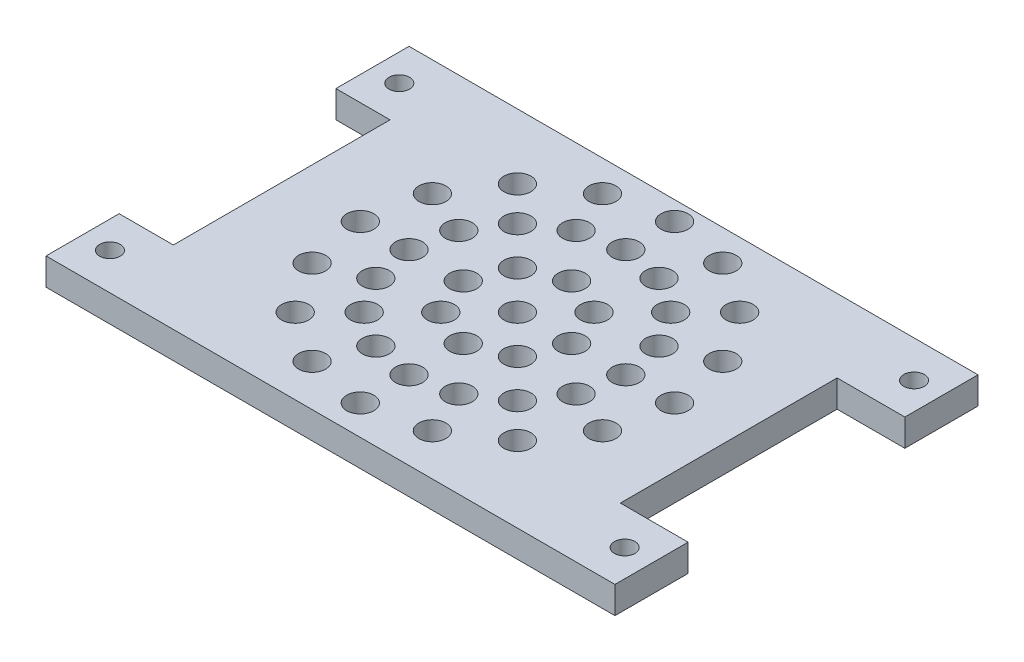
SolidWorks part; units mm, degrees
material "1060 Alloy"
ref_plane "Front Plane" through (0, 0, 0) normal (0, 0, 1) x (1, 0, 0)
ref_plane "Top Plane" through (0, 0, 0) normal (0, 1, 0) x (1, 0, 0)
ref_plane "Right Plane" through (0, 0, 0) normal (1, 0, 0) x (0, 0, -1)
sketch "Sketch1" plane through (0, 0, 0) normal (0, 1, 0) x (1, 0, 0)
  line L1 (-45.1884, 47.6545) -> (88.1616, 47.6545)
  line L2 (-45.1884, 47.6545) -> (-45.1884, -37.4355)
  line L3 (-45.1884, -37.4355) -> (88.1616, -37.4355)
  line L4 (88.1616, 47.6545) -> (88.1616, -37.4355)
  dimension "D1" = 133.35
  dimension "D2" = 85.09
extrude "Boss-Extrude1" add sketch "Sketch1" along normal blind 6.35
sketch "Sketch4" plane through (0, 6.35, 0) normal (0, 1, 0) x (1, 0, 0)
  line L0 (88.1616, -37.4355) -> (88.1616, 47.6545) construction
  line L1 (88.1616, 30.5095) -> (72.2866, 30.5095)
  line L2 (88.1616, 30.5095) -> (88.1616, -20.2905)
  line L3 (88.1616, -20.2905) -> (72.2866, -20.2905)
  line L4 (72.2866, 30.5095) -> (72.2866, -20.2905)
  line L5 (21.4866, 47.6545) -> (21.4866, -37.4355) construction
  line L6 (88.1616, 47.6545) -> (-45.1884, 47.6545) construction
  line L7 (-45.1884, -37.4355) -> (88.1616, -37.4355) construction
  line L12 (-45.1884, 5.1095) -> (88.1616, 5.1095) construction
  line L13 (-45.1884, 30.5095) -> (-45.1884, -20.2905)
  line L14 (-45.1884, 30.5095) -> (-32.4884, 30.5095)
  line L15 (-45.1884, -20.2905) -> (-32.4884, -20.2905)
  line L16 (-32.4884, 30.5095) -> (-32.4884, -20.2905)
  line L17 (-45.1884, 47.6545) -> (-45.1884, -37.4355) construction
  dimension "D1" = 15.875
  dimension "D2" = 50.8
  dimension "D3" = 12.7
  dimension "D4" = 50.8
extrude "Cut-Extrude8" cut sketch "Sketch4" against normal through all
sketch "Sketch2" plane through (0, 6.35, 0) normal (0, 1, 0) x (1, 0, 0)
  line L0 (88.1616, -37.4355) -> (88.1616, -20.2905) construction
  line L1 (-45.1884, -37.4355) -> (88.1616, -37.4355) construction
  line L2 (21.4866, 47.6545) -> (21.4866, -37.4355) construction
  line L3 (88.1616, 47.6545) -> (-45.1884, 47.6545) construction
  circle A0 centre (81.8116, -28.7995) radius 2.413
  circle A1 centre (81.8116, 39.0185) radius 2.413
  circle A4 centre (-38.8384, 39.0185) radius 2.413
  circle A5 centre (-38.8384, -28.7995) radius 2.413
  point P0 (81.8116, -28.7995)
  point P2 (81.8116, 39.0185)
  point P20 (-38.8384, 39.0185)
  point P21 (-38.8384, -28.7995)
  dimension "D5" = 4.826
  dimension "D1" = 6.35
  dimension "D3" = 8.636
  dimension "D4" = 8.636
extrude "Cut-Extrude1" cut sketch "Sketch2" against normal through all
sketch "Sketch3" plane through (0, 6.35, 0) normal (0, 1, 0) x (1, 0, 0)
  line L0 (88.1616, -37.4355) -> (88.1616, -20.2905) construction
  line L2 (88.1616, 47.6545) -> (-45.1884, 47.6545) construction
  circle A0 centre (21.4866, 6.3795) radius 3.175
  circle A1 centre (34.1866, 6.3795) radius 3.175
  circle A2 centre (46.8866, 6.3795) radius 3.175
  circle A3 centre (30.4669, -2.6007) radius 3.175
  circle A4 centre (21.4866, -6.3205) radius 3.175
  circle A5 centre (12.5064, -2.6007) radius 3.175
  circle A6 centre (8.7866, 6.3795) radius 3.175
  circle A7 centre (12.5064, 15.3598) radius 3.175
  circle A8 centre (21.4866, 19.0795) radius 3.175
  circle A9 centre (30.4669, 15.3598) radius 3.175
  circle A10 centre (44.9532, -3.3406) radius 3.175
  circle A11 centre (39.4471, -11.581) radius 3.175
  circle A12 centre (31.2068, -17.087) radius 3.175
  circle A13 centre (21.4866, -19.0205) radius 3.175
  circle A14 centre (11.7665, -17.087) radius 3.175
  circle A15 centre (3.5261, -11.581) radius 3.175
  circle A16 centre (-1.9799, -3.3406) radius 3.175
  circle A17 centre (-3.9134, 6.3795) radius 3.175
  circle A18 centre (-1.9799, 16.0997) radius 3.175
  circle A19 centre (3.5261, 24.34) radius 3.175
  circle A20 centre (11.7665, 29.8461) radius 3.175
  circle A21 centre (21.4866, 31.7795) radius 3.175
  circle A22 centre (31.2068, 29.8461) radius 3.175
  circle A23 centre (39.4471, 24.34) radius 3.175
  circle A24 centre (44.9532, 16.0997) radius 3.175
  circle A25 centre (58.3166, 6.3795) radius 3.175
  circle A26 centre (55.5131, -7.7147) radius 3.175
  circle A27 centre (47.5294, -19.6632) radius 3.175
  circle A28 centre (35.5809, -27.6469) radius 3.175
  circle A29 centre (21.4866, -30.4505) radius 3.175
  circle A30 centre (7.3924, -27.6469) radius 3.175
  circle A31 centre (-4.5561, -19.6632) radius 3.175
  circle A32 centre (-12.5399, -7.7147) radius 3.175
  circle A33 centre (-15.3434, 6.3795) radius 3.175
  circle A34 centre (-12.5399, 20.4738) radius 3.175
  circle A35 centre (-4.5561, 32.4223) radius 3.175
  circle A36 centre (7.3924, 40.406) radius 3.175
  circle A37 centre (21.4866, 43.2095) radius 3.175
  circle A38 centre (35.5809, 40.406) radius 3.175
  circle A39 centre (47.5294, 32.4223) radius 3.175
  circle A40 centre (55.5131, 20.4738) radius 3.175
  point P26 (21.4866, 6.3795)
  point P57 (21.4866, 6.3795)
  point P91 (21.4866, 6.3795)
  dimension "D1" = 6.35
  dimension "D5" = 6.35
  dimension "D9" = 6.35
  dimension "D2" = 66.675
  dimension "D3" = 41.275
  dimension "D4" = 12.7
  dimension "D10" = 11.43
  dimension "D6" = 2
  dimension "D7" = 8
  dimension "D8" = 16
  dimension "D11" = 16
extrude "Cut-Extrude7" cut sketch "Sketch3" against normal through all
